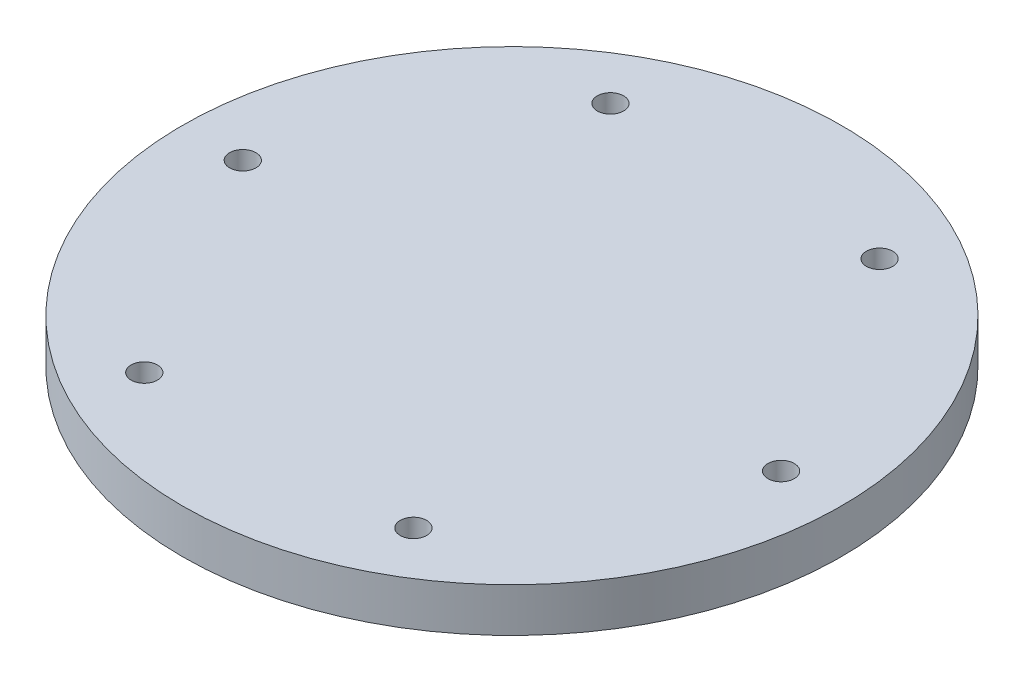
SolidWorks part; units mm, degrees
ref_plane "前基準面" through (0, 0, 0) normal (0, 0, 1) x (1, 0, 0)
ref_plane "上基準面" through (0, 0, 0) normal (0, 1, 0) x (1, 0, 0)
ref_plane "右基準面" through (0, 0, 0) normal (1, 0, 0) x (0, 0, -1)
sketch "草圖1" plane through (0, 0, 0) normal (0, 1, 0) x (1, 0, 0)
  line L0 (0, 0) -> (34.641, 0) construction
  line L1 (34.641, 0) -> (10.8253, 13.75) construction
  line L6 (8.6603, 15) -> (0, 0) construction
  line L7 (0.1554, 5.2692) -> (6.4045, 16.0929)
  line L9 (4.4856, 2.7692) -> (10.7346, 13.5929)
  line L10 (4.4856, -2.7692) -> (10.7346, -13.5929)
  line L11 (0.1554, -5.2692) -> (6.4045, -16.0929)
  line L12 (-4.641, -2.5) -> (-17.1391, -2.5)
  line L13 (-4.641, 2.5) -> (-17.1391, 2.5)
  arc A14 (12.6295, 11.8531) -> (10.7346, 13.5929) centre (0, 0) ccw
  circle A15 centre (34.641, 0) radius 30 construction
  circle A16 centre (0, 0) radius 4.641 construction
  arc A17 (10.8253, 13.75) -> (10.7295, 13.597) centre (8.6603, 15) ccw construction
  arc A18 (0.1554, 5.2692) -> (4.4856, 2.7692) centre (2.3205, 4.0192) ccw
  arc A19 (4.4856, -2.7692) -> (0.1554, -5.2692) centre (2.3205, -4.0192) ccw
  arc A20 (-4.641, -2.5) -> (-4.641, 2.5) centre (-4.641, 0) ccw
  circle A24 centre (4.641, 0) radius 2 construction
  arc A25 (12.6295, 11.8531) -> (12.6295, -11.8531) centre (34.641, 0) ccw
  arc A26 (13.8502, -11.9893) -> (13.8852, 12.0497) centre (34.641, 0) ccw construction
  arc A27 (13.8502, -11.9893) -> (13.8852, 12.0497) centre (0.0486, 0.0503) ccw construction
  arc A28 (3.9503, -16.864) -> (-16.5798, -5.011) centre (-17.3205, -30) ccw
  arc A29 (-16.5798, 5.011) -> (3.9503, 16.864) centre (-17.3205, 30) ccw
  arc A30 (3.9503, -16.864) -> (6.4045, -16.0929) centre (0, 0) ccw
  arc A31 (10.7346, -13.5929) -> (12.6295, -11.8531) centre (0, 0) ccw
  arc A32 (-16.5798, 5.011) -> (-17.1391, 2.5) centre (0, 0) ccw
  arc A33 (-17.1391, -2.5) -> (-16.5798, -5.011) centre (0, 0) ccw
  arc A34 (6.4045, 16.0929) -> (3.9503, 16.864) centre (0, 0) ccw
  circle A35 centre (0.0486, 0.0503) radius 1.25
  point P24 (0, 0)
  point P26 (0, 0)
  point P39 (0, 0)
  dimension "D1" = 60
  dimension "D4" = 24
  dimension "D3" = 90
  dimension "D5" = 4
  dimension "D6" = 30
  dimension "D2" = 5
  dimension "D9" = 2.5
  dimension "D10" = 60
  dimension "D11" = 34.641
  dimension "D12" = 25
  dimension "D13" = 18.315
  dimension "D7" = 3
  dimension "D8" = 3
extrude "填料-伸長1" add sketch "草圖1" along normal blind 20
sketch "草圖2" plane through (0, 20, 0) normal (0, 1, 0) x (1, 0, 0)
  line L0 (-84.9259, 0) -> (84.9259, 0) construction
  line L1 (0, 82.4287) -> (0, -69.8624) construction
  circle A2 centre (-61.25, 0) radius 3
  circle A3 centre (-30.625, 53.0441) radius 3
  circle A4 centre (0, 0) radius 75
  circle A10 centre (0, 0) radius 61.25 construction
  circle A16 centre (30.625, 53.0441) radius 3
  circle A17 centre (61.25, 0) radius 3
  circle A18 centre (30.625, -53.0441) radius 3
  circle A19 centre (-30.625, -53.0441) radius 3
  point P10 (27.4654, -35.3377)
  point P11 (0, 0)
  point P21 (0, 0)
  point P22 (0, 0)
  dimension "D1" = 6
  dimension "D2" = 13.75
  dimension "D3" = 150
  dimension "D4" = 6
extrude "填料-伸長2" add sketch "草圖2" along normal blind 10
fillet "圓角2" radius 2 9 edges at (-4.8205, 20, -8.3494) (-16.9062, 20, -3.7659) (-16.9062, 20, 3.7659) (-4.8205, 20, 8.3494) (5.1917, 20, 16.5241) (5.1917, 20, -16.5241) (11.7144, 20, 12.7582) (11.7144, 20, -12.7582) (9.641, 20, 0) curvature continuous yes second distance 2 first distance on face at (0, 20, 0)
